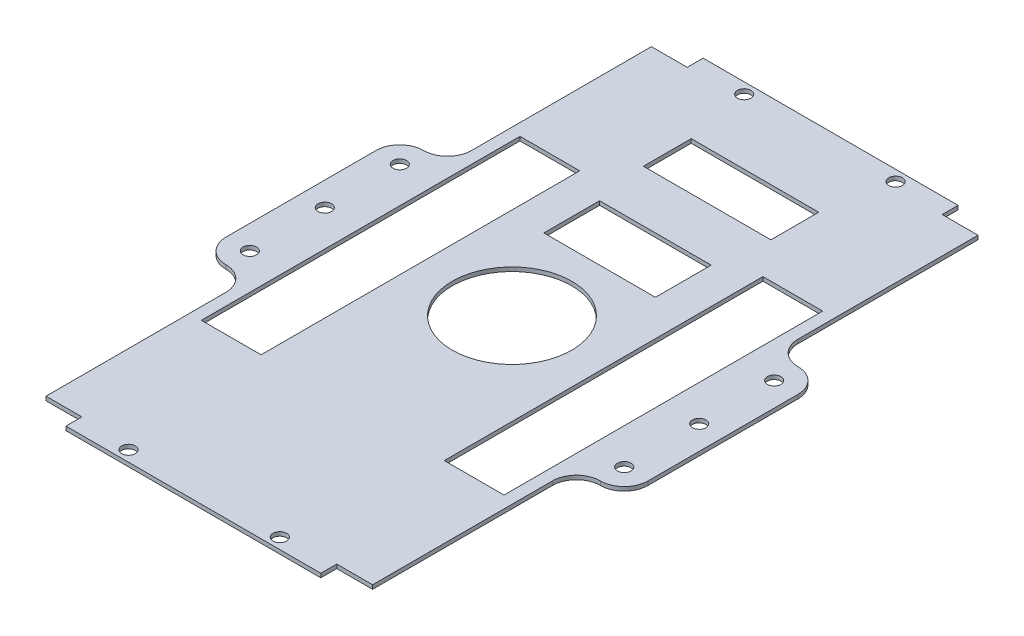
SolidWorks part; units mm, degrees
ref_plane "前视基准面" through (0, 0, 0) normal (0, 0, 1) x (1, 0, 0)
ref_plane "上视基准面" through (0, 0, 0) normal (0, 1, 0) x (1, 0, 0)
ref_plane "右视基准面" through (0, 0, 0) normal (1, 0, 0) x (0, 0, -1)
sketch "草图1" plane through (0, 0, 0) normal (0, 1, 0) x (1, 0, 0)
  line L0 (0, -55) -> (0, 55) construction
  line L4 (-55, 0) -> (55, 0) construction
  line L6 (-53, 18.8261) -> (-53, -18.8261)
  line L7 (0, 22) -> (14, 22)
  line L8 (14, 22) -> (14, 36)
  line L9 (14, 36) -> (-14, 36)
  line L10 (-14, 36) -> (-14, 22)
  line L11 (-14, 22) -> (0, 22)
  line L13 (-16, 61) -> (16, 61)
  line L14 (-41, 85.424) -> (-41, -13) construction
  line L15 (16, 61) -> (16, 49)
  line L16 (-41, 76) -> (-32, 76)
  line L17 (16, 49) -> (-16, 49)
  line L18 (-16, 61) -> (-16, 49)
  line L19 (-32, 76) -> (-32, 80)
  line L20 (33, 80) -> (-33, 80) construction
  line L21 (-32, 80) -> (32, 80)
  line L22 (-13.2842, 80) -> (13.2842, 80) construction
  line L23 (32, 76) -> (32, 80)
  line L24 (41, 76) -> (32, 76)
  line L26 (41, -76) -> (32, -76)
  line L27 (32, -76) -> (32, -80)
  line L28 (-32, -80) -> (32, -80)
  line L29 (-32, -76) -> (-32, -80)
  line L30 (-41, -76) -> (-32, -76)
  line L31 (-36.7273, 0) -> (36.7273, 0) construction
  line L32 (-41, -30.8261) -> (-41, -76)
  line L33 (0, -36.7273) -> (0, 36.7273) construction
  line L34 (41, -30.8261) -> (41, -76)
  line L35 (53, 18.8261) -> (53, -18.8261)
  line L36 (41, 30.8261) -> (41, 76)
  line L37 (-41, 80) -> (-41, -80) construction
  line L38 (-41, 30.8261) -> (-41, 76)
  line L41 (-38, 40) -> (-23, 40)
  line L43 (-23, 13) -> (-23, 40)
  line L45 (-23, -13) -> (-23, 13)
  line L53 (-38, 40) -> (-38, -40)
  line L54 (-23, -13) -> (-23, -40)
  line L55 (-38, -40) -> (-23, -40)
  line L56 (38, -40) -> (23, -40)
  line L57 (23, -13) -> (23, -40)
  line L58 (23, -13) -> (23, 13)
  line L59 (23, 13) -> (23, 40)
  line L60 (38, 40) -> (38, -40)
  line L61 (38, 40) -> (23, 40)
  circle A0 centre (-19, 77.3) radius 1.7
  circle A1 centre (19, 77.3) radius 1.7
  circle A2 centre (-19, -77.3) radius 1.7
  circle A3 centre (19, -77.3) radius 1.7
  arc A4 (-41, 30.8261) -> (-47, 24.8261) centre (-47, 30.8261) cw
  arc A5 (-47, 24.8261) -> (-53, 18.8261) centre (-47, 18.8261) ccw
  arc A6 (-47, -24.8261) -> (-53, -18.8261) centre (-47, -18.8261) cw
  arc A7 (-41, -30.8261) -> (-47, -24.8261) centre (-47, -30.8261) ccw
  arc A8 (41, -30.8261) -> (47, -24.8261) centre (47, -30.8261) cw
  arc A9 (47, -24.8261) -> (53, -18.8261) centre (47, -18.8261) ccw
  arc A10 (47, 24.8261) -> (53, 18.8261) centre (47, 18.8261) cw
  arc A11 (41, 30.8261) -> (47, 24.8261) centre (47, 30.8261) ccw
  circle A12 centre (0, 0) radius 15
  circle A13 centre (-47, 18.8261) radius 1.7
  circle A14 centre (-47, -18.8261) radius 1.7
  circle A15 centre (47, -18.8261) radius 1.7
  circle A16 centre (47, 18.8261) radius 1.7
  circle A17 centre (-47, 0) radius 1.7
  circle A18 centre (47, 0) radius 1.7
  arc A19 (-36, 2) -> (-36, -2) centre (-36, 0) ccw construction
  point P3 (0, -80)
  point P8 (0, 80)
  point P10 (-23, 0)
  point P11 (-41, 0)
  point P12 (41, 0)
  point P26 (0, 49)
  point P35 (-38, 0)
  point P36 (0, 80)
  point P41 (41, 0)
  point P46 (-41, 0)
  point P64 (-53, 0)
  point P88 (-23, 0)
  point P89 (-38, 0)
extrude "凸台-拉伸1" add sketch "草图1" along normal blind 1 contours L30 L29 L27 L26 L24 L23 L21 L19 L16 L11 L10 L9 L8 L7 L18 L13 L15 L17 region at (-49.8855, 0, -21.7116)
